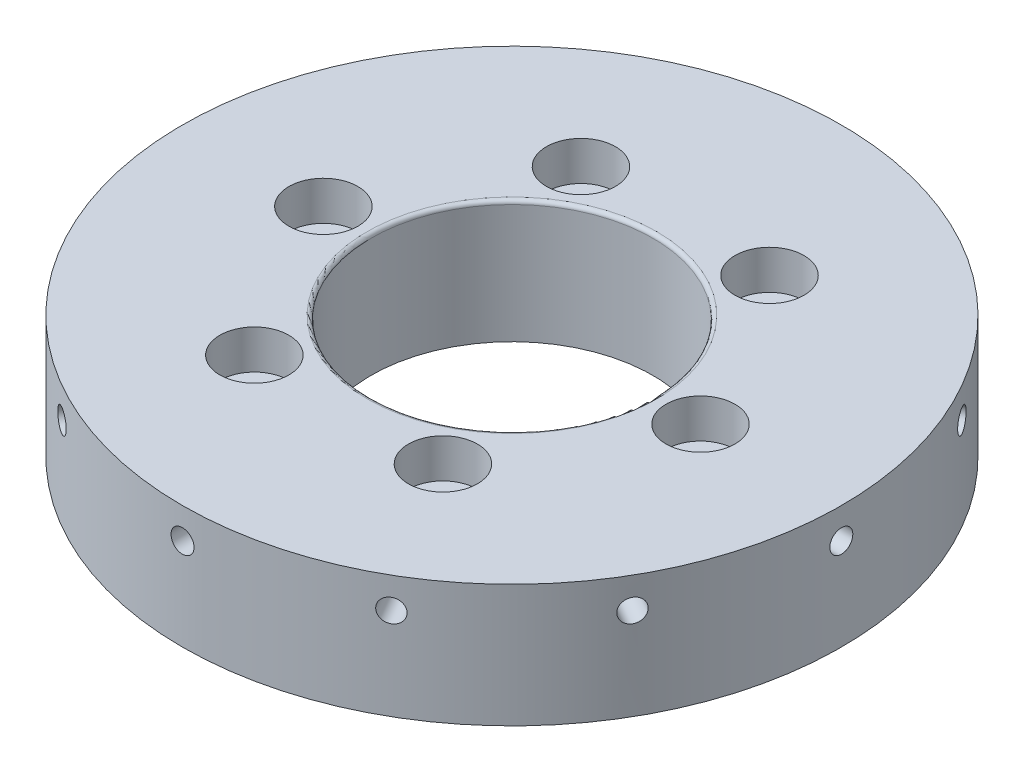
SolidWorks part; units mm, degrees
ref_plane "前视基准面" through (0, 0, 0) normal (0, 0, 1) x (1, 0, 0)
ref_plane "上视基准面" through (0, 0, 0) normal (0, 1, 0) x (1, 0, 0)
ref_plane "右视基准面" through (0, 0, 0) normal (1, 0, 0) x (0, 0, -1)
sketch "草图1" plane through (0, 0, 0) normal (0, 1, 0) x (1, 0, 0)
  circle A0 centre (0, 0) radius 43
  circle A1 centre (0, 0) radius 24.6 construction
  circle A2 centre (-24.6, 0) radius 2.5
  circle A3 centre (-12.3, 21.3042) radius 2.5
  circle A4 centre (12.3, 21.3042) radius 2.5
  circle A5 centre (24.6, 0) radius 2.5
  circle A6 centre (12.3, -21.3042) radius 2.5
  circle A7 centre (-12.3, -21.3042) radius 2.5
  circle A8 centre (0, 0) radius 18.4
  point P19 (0, 0)
  dimension "D1" = 6
  dimension "D2" = 86
extrude "凸台-拉伸1" add sketch "草图1" along normal blind 16
sketch "草图2" plane through (0, 0, 0) normal (0, -1, 0) x (1, 0, 0)
  circle A0 centre (0, 0) radius 24.6 construction
  circle A1 centre (-21.3042, -12.3) radius 4
  circle A2 centre (0, 24.6) radius 4
  circle A3 centre (21.3042, -12.3) radius 4
  point P17 (0, 0)
  dimension "D1" = 3
extrude "切除-拉伸1" cut sketch "草图2" against normal blind 3
sketch "草图4" plane through (0, 16, 0) normal (0, 1, 0) x (1, 0, 0)
  circle A0 centre (-24.6, 0) radius 4.5
  circle A1 centre (0, 0) radius 24.6 construction
  circle A2 centre (-12.3, 21.3042) radius 4.5
  circle A3 centre (12.3, 21.3042) radius 4.5
  circle A4 centre (24.6, 0) radius 4.5
  circle A5 centre (12.3, -21.3042) radius 4.5
  circle A6 centre (-12.3, -21.3042) radius 4.5
  point P16 (0, 0)
  dimension "D1" = 6
extrude "切除-拉伸2" cut sketch "草图4" against normal blind 5.1
ref_plane "基准面1" through (43, 0, 0) normal (1, 0, 0) x (0, 0, -1)
sketch "草图5" plane through (43, 0, 0) normal (1, 0, 0) x (0, 0, -1)
  circle A0 centre (0, 12) radius 1.5
extrude "切除-拉伸3" cut sketch "草图5" against normal blind 10
pattern_circular "阵列(圆周)1" count 12 every 30 about axis through (0, 16, 0) along (0, -1, 0) of "切除-拉伸3"
fillet "圆角1" radius 0.5 1 edges at (0, 16, 18.4)
